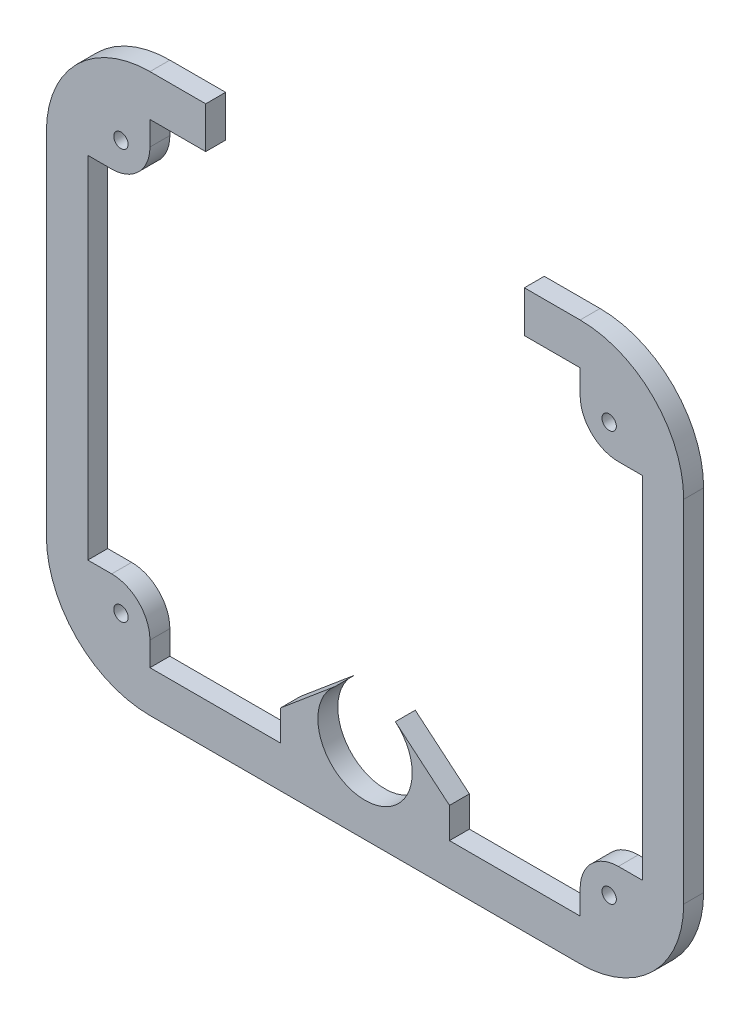
SolidWorks part; units mm, degrees
material "Delrin"
ref_plane "Front Plane" through (0, 0, 0) normal (0, 0, 1) x (1, 0, 0)
ref_plane "Top Plane" through (0, 0, 0) normal (0, 1, 0) x (1, 0, 0)
ref_plane "Right Plane" through (0, 0, 0) normal (1, 0, 0) x (0, 0, -1)
sketch "Sketch1" plane through (0, 0, 0) normal (0, 0, 1) x (1, 0, 0)
  line L0 (-17.145, -18.923) -> (-9.6321, -18.923)
  line L1 (17.145, 22.225) -> (-17.145, 22.225)
  line L2 (25.4, 13.97) -> (25.4, -13.97)
  line L3 (17.145, -22.225) -> (-17.145, -22.225)
  line L4 (-25.4, 13.97) -> (-25.4, -13.97)
  line L5 (25.4, 22.225) -> (-25.4, -22.225) construction
  line L6 (25.4, -22.225) -> (-25.4, 22.225) construction
  line L7 (9.6321, -18.923) -> (17.145, -18.923)
  line L8 (0, 0) -> (-25.0375, 21.0089) construction
  line L9 (-22.098, 13.97) -> (-17.145, 13.97)
  line L10 (-22.098, 13.97) -> (-22.098, -13.97)
  line L11 (-1000, 0) -> (49000, 0) construction
  line L12 (17.145, 18.923) -> (17.145, 13.97)
  line L13 (22.098, 13.97) -> (22.098, -13.97)
  line L14 (17.145, 18.923) -> (-17.145, 18.923)
  line L15 (-17.145, 13.97) -> (-17.145, 18.923)
  line L16 (17.145, 13.97) -> (22.098, 13.97)
  line L17 (-17.145, -18.923) -> (-17.145, -13.97)
  line L18 (0, 18.923) -> (0, -18.415) construction
  line L19 (-22.098, -13.97) -> (-17.145, -13.97)
  line L20 (17.145, -18.923) -> (17.145, -13.97)
  line L21 (2.4164, -12.8683) -> (9.6321, -18.923)
  line L22 (-2.4164, -12.8683) -> (-9.6321, -18.923)
  line L23 (22.098, -13.97) -> (17.145, -13.97)
  line L36 (17.145, -18.923) -> (-17.145, -18.923) construction
  arc A0 (-2.4164, -12.8683) -> (2.4164, -12.8683) centre (0, -15.748) ccw
  arc A1 (-17.145, 22.225) -> (-25.4, 13.97) centre (-17.145, 13.97) ccw
  arc A2 (17.145, 22.225) -> (25.4, 13.97) centre (17.145, 13.97) cw
  arc A3 (25.4, -13.97) -> (17.145, -22.225) centre (17.145, -13.97) cw
  arc A4 (-17.145, -22.225) -> (-25.4, -13.97) centre (-17.145, -13.97) cw
  arc A7 (17.145, 18.923) -> (22.098, 13.97) centre (17.145, 13.97) cw construction
  arc A8 (-17.145, 18.923) -> (-22.098, 13.97) centre (-17.145, 13.97) ccw construction
  circle A9 centre (-19.4575, 16.3268) radius 0.5715
  circle A10 centre (19.4575, 16.3268) radius 0.5715
  circle A11 centre (-19.4575, -16.3268) radius 0.5715
  circle A12 centre (19.4575, -16.3268) radius 0.5715
  arc A13 (-17.145, -18.923) -> (-22.098, -13.97) centre (-17.145, -13.97) cw construction
  arc A14 (22.098, -13.97) -> (17.145, -18.923) centre (17.145, -13.97) cw construction
  point P0 (0, 0)
  dimension "D4" = 7.5184
  dimension "D6" = 8.255
  dimension "D7" = 8.255
  dimension "D8" = 8.255
  dimension "D9" = 8.255
  dimension "D5" = 1.143
  dimension "D1" = 50.8
  dimension "D2" = 44.45
  dimension "D10" = 3.302
  dimension "D3" = 3.175
  dimension "D11" = 25.4
  dimension "D12" = 40
  dimension "D13" = 15.748
extrude "Boss-Extrude1" add sketch "Sketch1" along normal blind 1.5875
sketch "Sketch2" plane through (0, 0, 1.5875) normal (0, 0, 1) x (1, 0, 0)
  line L0 (-9.6321, -18.923) -> (-2.4164, -12.8683) construction
  line L1 (-9.6321, -18.923) -> (-6.731, -18.923)
  line L2 (-9.6321, -18.923) -> (-9.6321, -16.4887)
  line L3 (-9.6321, -16.4887) -> (-6.731, -16.4887)
  line L4 (-6.731, -18.923) -> (-6.731, -16.4887)
  line L5 (0, -1000) -> (0, 49000) construction
  line L6 (9.6321, -18.923) -> (9.6321, -16.4887)
  line L7 (9.6321, -16.4887) -> (6.731, -16.4887)
  line L8 (6.731, -18.923) -> (6.731, -16.4887)
  line L9 (9.6321, -18.923) -> (6.731, -18.923)
  line L10 (17.145, 18.923) -> (-17.145, 18.923) construction
  line L11 (-12.7, 18.923) -> (12.7, 18.923)
  line L12 (-12.7, 18.923) -> (-12.7, 22.225)
  line L13 (-12.7, 22.225) -> (12.7, 22.225)
  line L14 (12.7, 18.923) -> (12.7, 22.225)
  line L15 (17.145, 22.225) -> (-17.145, 22.225) construction
  arc A0 (-2.4164, -12.8683) -> (2.4164, -12.8683) centre (0, -15.748) ccw construction
  point P25 (0, 22.225)
  dimension "D1" = 6.731
  dimension "D2" = 25.4
extrude "Cut-Extrude1" cut sketch "Sketch2" against normal up to next
fillet "Fillet1" radius 3.048 4 edges at (17.145, 13.97, 0.7937) (17.145, -13.97, 0.7937) (-17.145, -13.97, 0.7937) (-17.145, 13.97, 0.7937)
